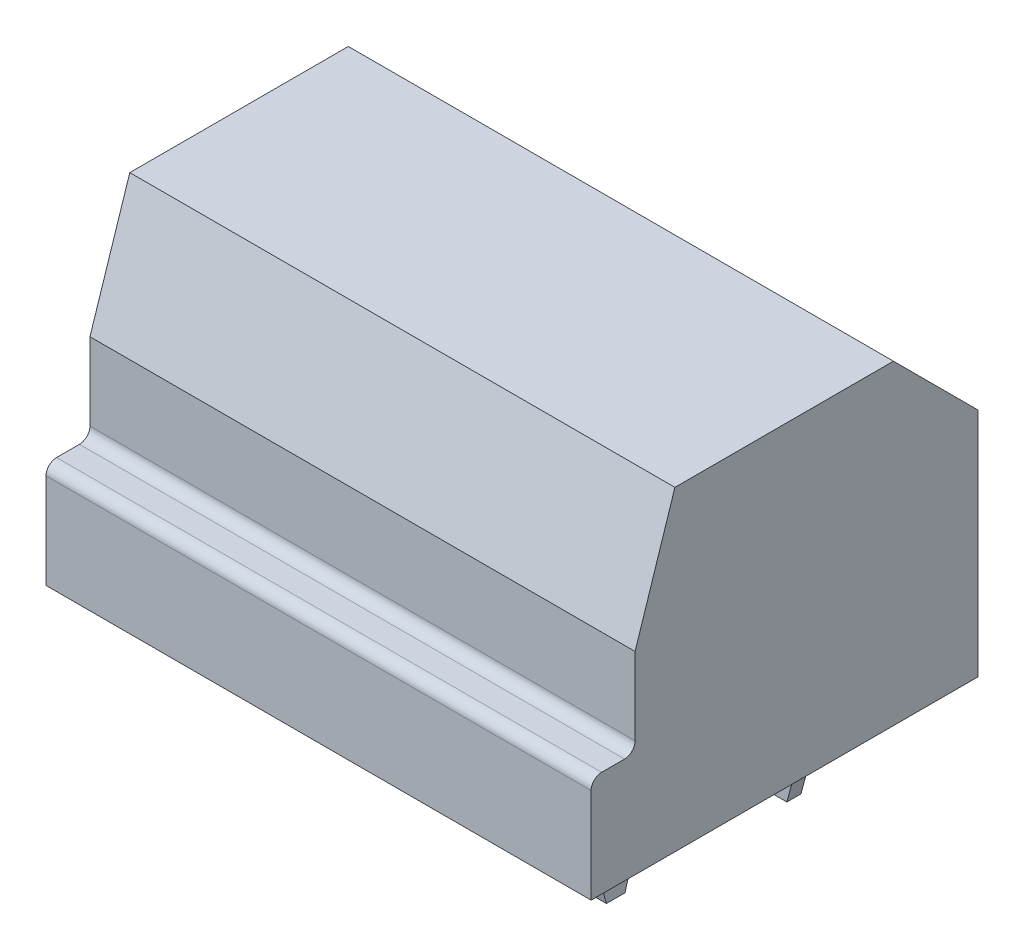
SolidWorks part; units mm, degrees
ref_plane "Front Plane" through (0, 0, 0) normal (0, 0, 1) x (1, 0, 0)
ref_plane "Top Plane" through (0, 0, 0) normal (0, 1, 0) x (1, 0, 0)
ref_plane "Right Plane" through (0, 0, 0) normal (1, 0, 0) x (0, 0, -1)
sketch "Sketch2" plane through (0, 0, 0) normal (1, 0, 0) x (0, 0, -1)
  line L0 (0, 0) -> (11, 0)
  line L5 (11, 0) -> (11, 6.5709)
  line L6 (11, 6.5709) -> (8.5958, 8.975)
  line L7 (8.5958, 8.975) -> (2.3818, 8.975)
  line L8 (2.3818, 8.975) -> (1.25, 5.5)
  line L9 (1.25, 5.5) -> (1.25, 3)
  line L10 (1.25, 3) -> (0, 3)
  line L11 (0, 3) -> (0, 0)
  dimension "D1" = 11
  dimension "D2" = 6.214
  dimension "D3" = 3.4
  dimension "D4" = 2.5
  dimension "D5" = 3
  dimension "D6" = 1.25
extrude "Boss-Extrude2" add sketch "Sketch2" along normal blind 15.5
sketch "Sketch3" plane through (0, 0, 0) normal (0, -1, 0) x (1, 0, 0)
  line L0 (13, -3) -> (15.5, -3) construction
  line L5 (12.8, -3.4) -> (13.2, -3.4)
  line L6 (12.8, -3.4) -> (12.8, -2.6)
  line L7 (12.8, -2.6) -> (13.2, -2.6)
  line L8 (13.2, -3.4) -> (13.2, -2.6)
  line L9 (12.8, -3.4) -> (13.2, -2.6) construction
  line L10 (12.8, -2.6) -> (13.2, -3.4) construction
  line L12 (15.5, 0) -> (15.5, -11) construction
  line L13 (12.6, -7.8) -> (13.4, -7.8)
  line L14 (12.6, -7.8) -> (12.6, -8.2)
  line L15 (12.6, -8.2) -> (13.4, -8.2)
  line L16 (13.4, -7.8) -> (13.4, -8.2)
  line L17 (12.6, -7.8) -> (13.4, -8.2) construction
  line L18 (12.6, -8.2) -> (13.4, -7.8) construction
  line L19 (13, -3) -> (13, -8) construction
  line L20 (13, -3) -> (13, 0) construction
  line L21 (15.5, 0) -> (0, 0) construction
  point P0 (13, -3)
  point P9 (13, -8)
  dimension "D1" = 2.5
  dimension "D2" = 0.8
  dimension "D3" = 0.4
  dimension "D4" = 5
  dimension "D5" = 3
extrude "Boss-Extrude3" add sketch "Sketch3" along normal blind 2.6
chamfer "Chamfer1" distance 0.5 angle 15 4 edges at (13, -2.6, -2.6) (13, -2.6, -3.4) (12.6, -2.6, -8) (13.4, -2.6, -8) first distance on face at (13, -1.3, -2.6) first distance on face at (13, -1.3, -3.4) first distance on face at (12.6, -1.3, -8) first distance on face at (13.4, -1.3, -8)
pattern_linear "LPattern1" count 4 spacing 3.5 along (-1, 0, 0) of "Boss-Extrude3", "Chamfer1"
sketch "Sketch4" plane through (0, 8.7854, -8.7854) normal (0, 0.7071, -0.7071) x (1, 0, 0)
  line L0 (13, -0.2681) -> (13, 3.1319) construction
  line L1 (14.25, 2.6819) -> (11.75, 2.6819)
  line L2 (14.25, 2.6819) -> (14.25, 0.1819)
  line L3 (14.25, 0.1819) -> (11.75, 0.1819)
  line L4 (11.75, 2.6819) -> (11.75, 0.1819)
  line L5 (14.25, 2.6819) -> (11.75, 0.1819) construction
  line L6 (14.25, 0.1819) -> (11.75, 2.6819) construction
  line L7 (15.5, -0.2681) -> (0, -0.2681) construction
  line L8 (15.5, 3.1319) -> (0, 3.1319) construction
  line L9 (13, 1.4319) -> (15.5, 1.4319) construction
  line L10 (15.5, 3.1319) -> (15.5, -0.2681) construction
  point P0 (13, 1.4319)
  point P12 (13, 1.4319)
  dimension "D1" = 2.5
  dimension "D2" = 2.5
  dimension "D3" = 2.5
extrude "Cut-Extrude1" cut sketch "Sketch4" against normal blind 2
chamfer "Chamfer2" distance 1.1 angle 25 4 edges at (13, 5.4749, -9.2676) (14.25, 6.3588, -8.3837) (13, 7.2426, -7.4998) (11.75, 6.3588, -8.3837) first distance on face at (13, 6.182, -9.9747) first distance on face at (14.25, 7.0659, -9.0908) first distance on face at (13, 7.9497, -8.2069) first distance on face at (11.75, 7.0659, -9.0908)
fillet "Fillet1" radius 0.6 8 edges at (14.25, 6.5709, -10.3636) (11.75, 6.5709, -10.3636) (11.75, 8.3387, -8.5958) (14.25, 8.3387, -8.5958) (13.9935, 6.0451, -9.4751) (12.0065, 6.0451, -9.4751) (12.0065, 7.4502, -8.0701) (13.9935, 7.4502, -8.0701)
pattern_linear "LPattern2" count 4 spacing 3.5 along (-1, 0, 0) of "Fillet1", "Chamfer2", "Cut-Extrude1"
fillet "Fillet2" radius 0.3 2 edges at (7.75, 3, -1.25) (7.75, 3, 0)
